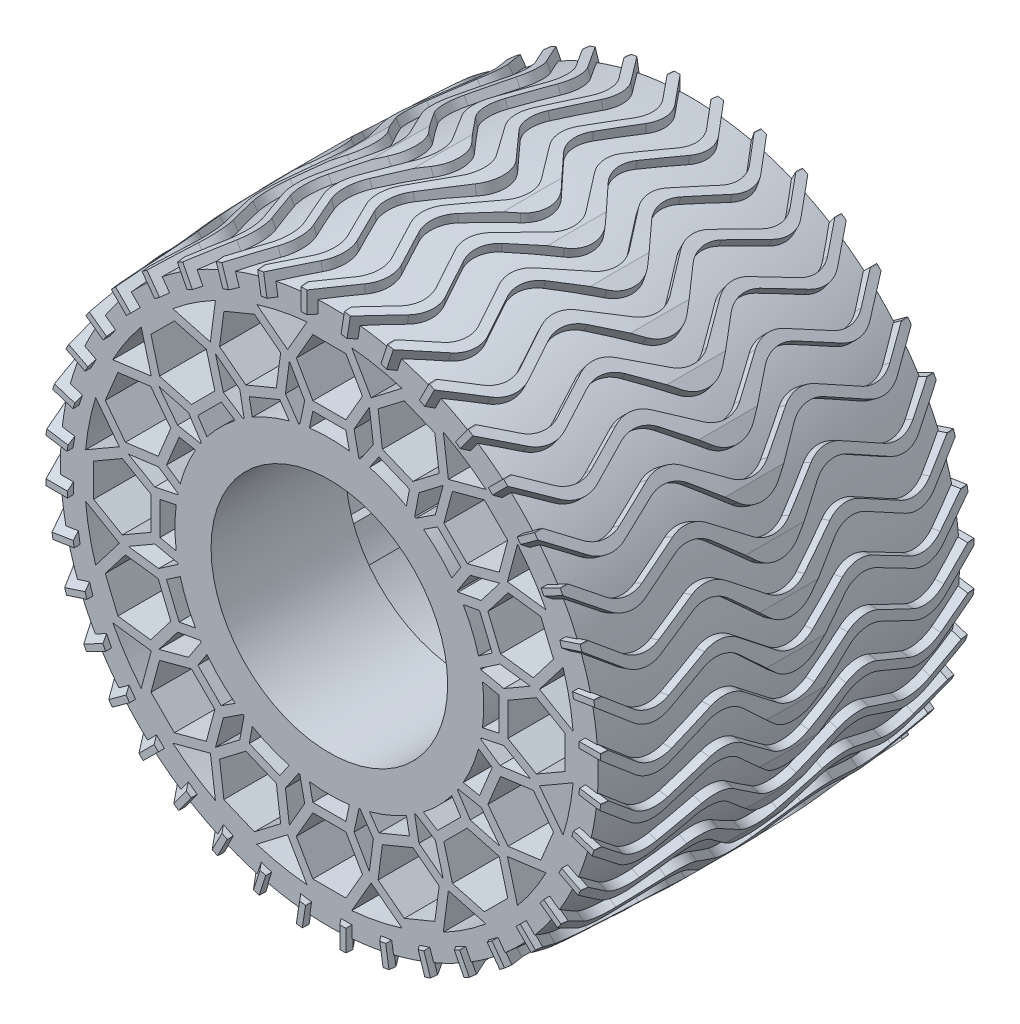
SolidWorks part; units mm, degrees
ref_plane "Alzado" through (0, 0, 0) normal (0, 0, 1) x (1, 0, 0)
ref_plane "Planta" through (0, 0, 0) normal (0, 1, 0) x (1, 0, 0)
ref_plane "Vista lateral" through (0, 0, 0) normal (1, 0, 0) x (0, 0, -1)
sketch "Croquis3" plane through (0, 0, 0) normal (1, 0, 0) x (0, 0, -1)
  line L0 (-55, 0) -> (55, 0) construction
  point P4 (0, 0)
  dimension "D1" = 110
sketch "Croquis2" plane through (0, 0, 0) normal (1, 0, 0) x (0, 0, -1)
  line L0 (0, 0) -> (0, 81.3) construction
  line L1 (-60, 81.3) -> (60, 81.3)
  line L2 (0, 81.3) -> (0, 89.3) construction
  line L3 (0, 89.3) -> (0, 92.3) construction
  line L4 (-60, 89.3) -> (60, 89.3) construction
  line L5 (-60, 89.3) -> (-60, 81.3)
  line L6 (60, 89.3) -> (60, 81.3)
  line L7 (-60, 39.3) -> (-15.3, 39.3)
  line L8 (60, 39.3) -> (60, 51.3)
  line L9 (60, 51.3) -> (-60, 51.3)
  line L10 (-60, 51.3) -> (-60, 39.3)
  line L11 (-50, 47.9) -> (50, 47.9)
  line L14 (50, 39.3) -> (60, 39.3)
  line L15 (-15.3, 39.3) -> (-15.3, 42.3)
  line L16 (-15.3, 42.3) -> (-50, 42.3)
  line L17 (-50, 42.3) -> (-50, 47.9)
  line L20 (50, 39.3) -> (50, 47.9)
  arc A0 (60, 89.3) -> (-60, 89.3) centre (0, -509.2) ccw
  point P6 (0, 81.3)
  point P11 (0, 89.3)
  point P15 (0, 39.3)
  point P18 (0, 51.3)
  point P20 (0, 47.9)
  dimension "D2" = 120
  dimension "D3" = 8
  dimension "D4" = 3
  dimension "D5" = 12
  dimension "D6" = 39.3
  dimension "D7" = 100
  dimension "D8" = 15.3
  dimension "D10" = 30
  dimension "D12" = 3
  dimension "D13" = 5.6
revolve "Revolución1" add sketch "Croquis2" angle 360 about L0
sketch "Croquis4" plane through (0, 0, 0) normal (0, 0, 1) x (1, 0, 0)
  line L0 (-72.3472, 37.7855) -> (-77.8756, 24.4389)
  line L1 (77.8756, 24.4389) -> (72.3472, 37.7855)
  line L2 (62.5953, 52.3803) -> (52.3803, 62.5953)
  line L3 (37.7855, 72.3472) -> (24.4389, 77.8756)
  line L4 (7.2231, 81.3) -> (-7.2231, 81.3)
  line L5 (-24.4389, 77.8756) -> (-37.7855, 72.3472)
  line L6 (-52.3803, 62.5953) -> (-62.5953, 52.3803)
  line L7 (-81.3, 7.2231) -> (-81.3, -7.2231)
  line L8 (-77.8756, -24.4389) -> (-72.3472, -37.7855)
  line L9 (-62.5953, -52.3803) -> (-52.3803, -62.5953)
  line L10 (-37.7855, -72.3472) -> (-24.4389, -77.8756)
  line L11 (-7.2231, -81.3) -> (7.2231, -81.3)
  line L12 (24.4389, -77.8756) -> (37.7855, -72.3472)
  line L13 (52.3803, -62.5953) -> (62.5953, -52.3803)
  line L14 (72.3472, -37.7855) -> (77.8756, -24.4389)
  line L15 (81.3, -7.2231) -> (81.3, 7.2231)
  line L16 (0, 0) -> (81.3, 0) construction
  line L17 (15.3929, 77.3853) -> (-14.444, -72.6147) construction
  line L18 (-14.9184, 75) -> (14.9184, -75) construction
  line L19 (0, 0) -> (0, 81.3) construction
  line L20 (-7.2231, 81.3) -> (-13.8786, 69.7724)
  line L31 (-13.2819, 66.7724) -> (-8.2005, 57.9713)
  line L32 (-8.2005, 57.9713) -> (-9.9128, 49.8349)
  line L33 (-7.1326, 48.4781) -> (-5.4911, 56.2784)
  line L34 (10.9821, 68.7892) -> (5.4911, 78.3)
  line L35 (5.4911, 78.3) -> (-5.4911, 78.3)
  line L36 (-5.4911, 78.3) -> (-10.9821, 68.7892)
  line L37 (-10.9821, 68.7892) -> (-5.4911, 59.2784)
  line L38 (-5.4911, 59.2784) -> (5.4911, 59.2784)
  line L39 (5.4911, 59.2784) -> (10.9821, 68.7892)
  line L40 (-5.4911, 56.2784) -> (5.4911, 56.2784)
  line L41 (5.4911, 56.2784) -> (7.1326, 48.4781)
  line L42 (36.4707, 59.3502) -> (35.0372, 70.2384)
  line L43 (35.0372, 70.2384) -> (24.891, 74.4411)
  line L44 (24.891, 74.4411) -> (16.1783, 67.7556)
  line L45 (16.1783, 67.7556) -> (17.6118, 56.8674)
  line L46 (17.6118, 56.8674) -> (27.7579, 52.6647)
  line L47 (8.2005, 57.9713) -> (9.9128, 49.8349)
  line L48 (27.7579, 52.6647) -> (36.4707, 59.3502)
  line L49 (13.2819, 66.7724) -> (8.2005, 57.9713)
  line L50 (7.2231, 81.3) -> (13.8786, 69.7724)
  line L51 (24.4389, 77.8756) -> (13.8786, 69.7724)
  line L52 (13.2819, 66.7724) -> (14.6083, 56.6967)
  line L53 (11.9621, 47.5174) -> (16.4637, 54.0958)
  line L54 (14.6083, 56.6967) -> (9.9128, 49.8349)
  line L55 (26.6099, 49.8931) -> (25.1414, 42.0584)
  line L56 (29.7609, 50.4203) -> (28.2292, 42.248)
  line L57 (16.4637, 54.0958) -> (26.6099, 49.8931)
  line L58 (37.8235, 56.6069) -> (29.7609, 50.4203)
  line L59 (37.7855, 72.3472) -> (39.5229, 59.1502)
  line L60 (56.4068, 40.8757) -> (59.2492, 51.4837)
  line L61 (59.2492, 51.4837) -> (51.4837, 59.2492)
  line L62 (51.4837, 59.2492) -> (40.8757, 56.4068)
  line L63 (40.8757, 56.4068) -> (38.0334, 45.7989)
  line L64 (38.0334, 45.7989) -> (45.7989, 38.0334)
  line L65 (45.7989, 38.0334) -> (56.4068, 40.8757)
  line L66 (52.3803, 62.5953) -> (39.5229, 59.1502)
  line L67 (37.8235, 56.6069) -> (35.1932, 46.7905)
  line L68 (29.2357, 39.3227) -> (35.912, 43.6776)
  line L69 (35.1932, 46.7905) -> (28.2292, 42.248)
  line L70 (43.6776, 35.912) -> (39.3227, 29.2357)
  line L71 (46.7905, 35.1932) -> (42.248, 28.2292)
  line L72 (35.912, 43.6776) -> (43.6776, 35.912)
  line L73 (56.6069, 37.8235) -> (46.7905, 35.1932)
  line L74 (62.5953, 52.3803) -> (59.1502, 39.5229)
  line L75 (67.7556, 16.1783) -> (74.4411, 24.891)
  line L76 (74.4411, 24.891) -> (70.2384, 35.0372)
  line L77 (70.2384, 35.0372) -> (59.3502, 36.4707)
  line L78 (59.3502, 36.4707) -> (52.6647, 27.7579)
  line L79 (52.6647, 27.7579) -> (56.8674, 17.6118)
  line L80 (56.8674, 17.6118) -> (67.7556, 16.1783)
  line L81 (72.3472, 37.7855) -> (59.1502, 39.5229)
  line L82 (56.6069, 37.8235) -> (50.4203, 29.7609)
  line L83 (42.0584, 25.1414) -> (49.8931, 26.6099)
  line L84 (50.4203, 29.7609) -> (42.248, 28.2292)
  line L85 (54.0958, 16.4637) -> (47.5174, 11.9621)
  line L86 (56.6967, 14.6083) -> (49.8349, 9.9128)
  line L87 (49.8931, 26.6099) -> (54.0958, 16.4637)
  line L88 (66.7724, 13.2819) -> (56.6967, 14.6083)
  line L89 (77.8756, 24.4389) -> (69.7724, 13.8786)
  line L90 (68.7892, -10.9821) -> (78.3, -5.4911)
  line L91 (78.3, -5.4911) -> (78.3, 5.4911)
  line L92 (78.3, 5.4911) -> (68.7892, 10.9821)
  line L93 (68.7892, 10.9821) -> (59.2784, 5.4911)
  line L94 (59.2784, 5.4911) -> (59.2784, -5.4911)
  line L95 (59.2784, -5.4911) -> (68.7892, -10.9821)
  line L96 (81.3, 7.2231) -> (69.7724, 13.8786)
  line L97 (66.7724, 13.2819) -> (57.9713, 8.2005)
  line L98 (48.4781, 7.1326) -> (56.2784, 5.4911)
  line L99 (57.9713, 8.2005) -> (49.8349, 9.9128)
  line L100 (56.2784, -5.4911) -> (48.4781, -7.1326)
  line L101 (57.9713, -8.2005) -> (49.8349, -9.9128)
  line L102 (56.2784, 5.4911) -> (56.2784, -5.4911)
  line L103 (66.7724, -13.2819) -> (57.9713, -8.2005)
  line L104 (81.3, -7.2231) -> (69.7724, -13.8786)
  line L105 (59.3502, -36.4707) -> (70.2384, -35.0372)
  line L106 (70.2384, -35.0372) -> (74.4411, -24.891)
  line L107 (74.4411, -24.891) -> (67.7556, -16.1783)
  line L108 (67.7556, -16.1783) -> (56.8674, -17.6118)
  line L109 (56.8674, -17.6118) -> (52.6647, -27.7579)
  line L110 (52.6647, -27.7579) -> (59.3502, -36.4707)
  line L111 (77.8756, -24.4389) -> (69.7724, -13.8786)
  line L112 (66.7724, -13.2819) -> (56.6967, -14.6083)
  line L113 (47.5174, -11.9621) -> (54.0958, -16.4637)
  line L114 (56.6967, -14.6083) -> (49.8349, -9.9128)
  line L115 (49.8931, -26.6099) -> (42.0584, -25.1414)
  line L116 (50.4203, -29.7609) -> (42.248, -28.2292)
  line L117 (54.0958, -16.4637) -> (49.8931, -26.6099)
  line L118 (56.6069, -37.8235) -> (50.4203, -29.7609)
  line L119 (72.3472, -37.7855) -> (59.1502, -39.5229)
  line L120 (40.8757, -56.4068) -> (51.4837, -59.2492)
  line L121 (51.4837, -59.2492) -> (59.2492, -51.4837)
  line L122 (59.2492, -51.4837) -> (56.4068, -40.8757)
  line L123 (56.4068, -40.8757) -> (45.7989, -38.0334)
  line L124 (45.7989, -38.0334) -> (38.0334, -45.7989)
  line L125 (38.0334, -45.7989) -> (40.8757, -56.4068)
  line L126 (62.5953, -52.3803) -> (59.1502, -39.5229)
  line L127 (56.6069, -37.8235) -> (46.7905, -35.1932)
  line L128 (39.3227, -29.2357) -> (43.6776, -35.912)
  line L129 (46.7905, -35.1932) -> (42.248, -28.2292)
  line L130 (35.912, -43.6776) -> (29.2357, -39.3227)
  line L131 (35.1932, -46.7905) -> (28.2292, -42.248)
  line L132 (43.6776, -35.912) -> (35.912, -43.6776)
  line L133 (37.8235, -56.6069) -> (35.1932, -46.7905)
  line L134 (52.3803, -62.5953) -> (39.5229, -59.1502)
  line L135 (16.1783, -67.7556) -> (24.891, -74.4411)
  line L136 (24.891, -74.4411) -> (35.0372, -70.2384)
  line L137 (35.0372, -70.2384) -> (36.4707, -59.3502)
  line L138 (36.4707, -59.3502) -> (27.7579, -52.6647)
  line L139 (27.7579, -52.6647) -> (17.6118, -56.8674)
  line L140 (17.6118, -56.8674) -> (16.1783, -67.7556)
  line L141 (37.7855, -72.3472) -> (39.5229, -59.1502)
  line L142 (37.8235, -56.6069) -> (29.7609, -50.4203)
  line L143 (25.1414, -42.0584) -> (26.6099, -49.8931)
  line L144 (29.7609, -50.4203) -> (28.2292, -42.248)
  line L145 (16.4637, -54.0958) -> (11.9621, -47.5174)
  line L146 (14.6083, -56.6967) -> (9.9128, -49.8349)
  line L147 (26.6099, -49.8931) -> (16.4637, -54.0958)
  line L148 (13.2819, -66.7724) -> (14.6083, -56.6967)
  line L149 (24.4389, -77.8756) -> (13.8786, -69.7724)
  line L150 (-10.9821, -68.7892) -> (-5.4911, -78.3)
  line L151 (-5.4911, -78.3) -> (5.4911, -78.3)
  line L152 (5.4911, -78.3) -> (10.9821, -68.7892)
  line L153 (10.9821, -68.7892) -> (5.4911, -59.2784)
  line L154 (5.4911, -59.2784) -> (-5.4911, -59.2784)
  line L155 (-5.4911, -59.2784) -> (-10.9821, -68.7892)
  line L156 (7.2231, -81.3) -> (13.8786, -69.7724)
  line L157 (13.2819, -66.7724) -> (8.2005, -57.9713)
  line L158 (7.1326, -48.4781) -> (5.4911, -56.2784)
  line L159 (8.2005, -57.9713) -> (9.9128, -49.8349)
  line L160 (-5.4911, -56.2784) -> (-7.1326, -48.4781)
  line L161 (-8.2005, -57.9713) -> (-9.9128, -49.8349)
  line L162 (5.4911, -56.2784) -> (-5.4911, -56.2784)
  line L163 (-13.2819, -66.7724) -> (-8.2005, -57.9713)
  line L164 (-7.2231, -81.3) -> (-13.8786, -69.7724)
  line L165 (-36.4707, -59.3502) -> (-35.0372, -70.2384)
  line L166 (-35.0372, -70.2384) -> (-24.891, -74.4411)
  line L167 (-24.891, -74.4411) -> (-16.1783, -67.7556)
  line L168 (-16.1783, -67.7556) -> (-17.6118, -56.8674)
  line L169 (-17.6118, -56.8674) -> (-27.7579, -52.6647)
  line L170 (-27.7579, -52.6647) -> (-36.4707, -59.3502)
  line L171 (-24.4389, -77.8756) -> (-13.8786, -69.7724)
  line L172 (-13.2819, -66.7724) -> (-14.6083, -56.6967)
  line L173 (-11.9621, -47.5174) -> (-16.4637, -54.0958)
  line L174 (-14.6083, -56.6967) -> (-9.9128, -49.8349)
  line L175 (-26.6099, -49.8931) -> (-25.1414, -42.0584)
  line L176 (-29.7609, -50.4203) -> (-28.2292, -42.248)
  line L177 (-16.4637, -54.0958) -> (-26.6099, -49.8931)
  line L178 (-37.8235, -56.6069) -> (-29.7609, -50.4203)
  line L179 (-37.7855, -72.3472) -> (-39.5229, -59.1502)
  line L180 (-56.4068, -40.8757) -> (-59.2492, -51.4837)
  line L181 (-59.2492, -51.4837) -> (-51.4837, -59.2492)
  line L182 (-51.4837, -59.2492) -> (-40.8757, -56.4068)
  line L183 (-40.8757, -56.4068) -> (-38.0334, -45.7989)
  line L184 (-38.0334, -45.7989) -> (-45.7989, -38.0334)
  line L185 (-45.7989, -38.0334) -> (-56.4068, -40.8757)
  line L186 (-52.3803, -62.5953) -> (-39.5229, -59.1502)
  line L187 (-37.8235, -56.6069) -> (-35.1932, -46.7905)
  line L188 (-29.2357, -39.3227) -> (-35.912, -43.6776)
  line L189 (-35.1932, -46.7905) -> (-28.2292, -42.248)
  line L190 (-43.6776, -35.912) -> (-39.3227, -29.2357)
  line L191 (-46.7905, -35.1932) -> (-42.248, -28.2292)
  line L192 (-35.912, -43.6776) -> (-43.6776, -35.912)
  line L193 (-56.6069, -37.8235) -> (-46.7905, -35.1932)
  line L194 (-62.5953, -52.3803) -> (-59.1502, -39.5229)
  line L195 (-67.7556, -16.1783) -> (-74.4411, -24.891)
  line L196 (-74.4411, -24.891) -> (-70.2384, -35.0372)
  line L197 (-70.2384, -35.0372) -> (-59.3502, -36.4707)
  line L198 (-59.3502, -36.4707) -> (-52.6647, -27.7579)
  line L199 (-52.6647, -27.7579) -> (-56.8674, -17.6118)
  line L200 (-56.8674, -17.6118) -> (-67.7556, -16.1783)
  line L201 (-72.3472, -37.7855) -> (-59.1502, -39.5229)
  line L202 (-56.6069, -37.8235) -> (-50.4203, -29.7609)
  line L203 (-42.0584, -25.1414) -> (-49.8931, -26.6099)
  line L204 (-50.4203, -29.7609) -> (-42.248, -28.2292)
  line L205 (-54.0958, -16.4637) -> (-47.5174, -11.9621)
  line L206 (-56.6967, -14.6083) -> (-49.8349, -9.9128)
  line L207 (-49.8931, -26.6099) -> (-54.0958, -16.4637)
  line L208 (-66.7724, -13.2819) -> (-56.6967, -14.6083)
  line L209 (-77.8756, -24.4389) -> (-69.7724, -13.8786)
  line L210 (-68.7892, 10.9821) -> (-78.3, 5.4911)
  line L211 (-78.3, 5.4911) -> (-78.3, -5.4911)
  line L212 (-78.3, -5.4911) -> (-68.7892, -10.9821)
  line L213 (-68.7892, -10.9821) -> (-59.2784, -5.4911)
  line L214 (-59.2784, -5.4911) -> (-59.2784, 5.4911)
  line L215 (-59.2784, 5.4911) -> (-68.7892, 10.9821)
  line L216 (-81.3, -7.2231) -> (-69.7724, -13.8786)
  line L217 (-66.7724, -13.2819) -> (-57.9713, -8.2005)
  line L218 (-48.4781, -7.1326) -> (-56.2784, -5.4911)
  line L219 (-57.9713, -8.2005) -> (-49.8349, -9.9128)
  line L220 (-56.2784, 5.4911) -> (-48.4781, 7.1326)
  line L221 (-57.9713, 8.2005) -> (-49.8349, 9.9128)
  line L222 (-56.2784, -5.4911) -> (-56.2784, 5.4911)
  line L223 (-66.7724, 13.2819) -> (-57.9713, 8.2005)
  line L224 (-81.3, 7.2231) -> (-69.7724, 13.8786)
  line L225 (-59.3502, 36.4707) -> (-70.2384, 35.0372)
  line L226 (-70.2384, 35.0372) -> (-74.4411, 24.891)
  line L227 (-74.4411, 24.891) -> (-67.7556, 16.1783)
  line L228 (-67.7556, 16.1783) -> (-56.8674, 17.6118)
  line L229 (-56.8674, 17.6118) -> (-52.6647, 27.7579)
  line L230 (-52.6647, 27.7579) -> (-59.3502, 36.4707)
  line L231 (-77.8756, 24.4389) -> (-69.7724, 13.8786)
  line L232 (-66.7724, 13.2819) -> (-56.6967, 14.6083)
  line L233 (-47.5174, 11.9621) -> (-54.0958, 16.4637)
  line L234 (-56.6967, 14.6083) -> (-49.8349, 9.9128)
  line L235 (-49.8931, 26.6099) -> (-42.0584, 25.1414)
  line L236 (-50.4203, 29.7609) -> (-42.248, 28.2292)
  line L237 (-54.0958, 16.4637) -> (-49.8931, 26.6099)
  line L238 (-56.6069, 37.8235) -> (-50.4203, 29.7609)
  line L239 (-72.3472, 37.7855) -> (-59.1502, 39.5229)
  line L240 (-40.8757, 56.4068) -> (-51.4837, 59.2492)
  line L241 (-51.4837, 59.2492) -> (-59.2492, 51.4837)
  line L242 (-59.2492, 51.4837) -> (-56.4068, 40.8757)
  line L243 (-56.4068, 40.8757) -> (-45.7989, 38.0334)
  line L244 (-45.7989, 38.0334) -> (-38.0334, 45.7989)
  line L245 (-38.0334, 45.7989) -> (-40.8757, 56.4068)
  line L246 (-62.5953, 52.3803) -> (-59.1502, 39.5229)
  line L247 (-56.6069, 37.8235) -> (-46.7905, 35.1932)
  line L248 (-39.3227, 29.2357) -> (-43.6776, 35.912)
  line L249 (-46.7905, 35.1932) -> (-42.248, 28.2292)
  line L250 (-35.912, 43.6776) -> (-29.2357, 39.3227)
  line L251 (-35.1932, 46.7905) -> (-28.2292, 42.248)
  line L252 (-43.6776, 35.912) -> (-35.912, 43.6776)
  line L253 (-37.8235, 56.6069) -> (-35.1932, 46.7905)
  line L254 (-52.3803, 62.5953) -> (-39.5229, 59.1502)
  line L255 (-16.1783, 67.7556) -> (-24.891, 74.4411)
  line L256 (-24.891, 74.4411) -> (-35.0372, 70.2384)
  line L257 (-35.0372, 70.2384) -> (-36.4707, 59.3502)
  line L258 (-36.4707, 59.3502) -> (-27.7579, 52.6647)
  line L259 (-27.7579, 52.6647) -> (-17.6118, 56.8674)
  line L260 (-17.6118, 56.8674) -> (-16.1783, 67.7556)
  line L261 (-37.7855, 72.3472) -> (-39.5229, 59.1502)
  line L262 (-37.8235, 56.6069) -> (-29.7609, 50.4203)
  line L263 (-25.1414, 42.0584) -> (-26.6099, 49.8931)
  line L264 (-29.7609, 50.4203) -> (-28.2292, 42.248)
  line L265 (-16.4637, 54.0958) -> (-11.9621, 47.5174)
  line L266 (-14.6083, 56.6967) -> (-9.9128, 49.8349)
  line L267 (-26.6099, 49.8931) -> (-16.4637, 54.0958)
  line L268 (-13.2819, 66.7724) -> (-14.6083, 56.6967)
  line L269 (-24.4389, 77.8756) -> (-13.8786, 69.7724)
  arc A0 (-24.1281, 77.6371) -> (-37.8366, 71.9589) centre (0, 0) ccw construction
  circle A1 centre (0, 0) radius 81.3 construction
  circle A5 centre (0, 68.7892) radius 9.5108 construction
  arc A9 (-39.3227, 29.2357) -> (-42.0584, 25.1414) centre (0, 0) ccw
  arc A41 (7.419, 80.9608) -> (-7.419, 80.9608) centre (0, 0) ccw construction
  arc A42 (37.8366, 71.9589) -> (24.1281, 77.6371) centre (0, 0) ccw construction
  arc A43 (62.4939, 52.0019) -> (52.0019, 62.4939) centre (0, 0) ccw construction
  arc A44 (77.6371, 24.1281) -> (71.9589, 37.8366) centre (0, 0) ccw construction
  arc A45 (80.9608, -7.419) -> (80.9608, 7.419) centre (0, 0) ccw construction
  arc A46 (71.9589, -37.8366) -> (77.6371, -24.1281) centre (0, 0) ccw construction
  arc A47 (52.0019, -62.4939) -> (62.4939, -52.0019) centre (0, 0) ccw construction
  arc A48 (24.1281, -77.6371) -> (37.8366, -71.9589) centre (0, 0) ccw construction
  arc A49 (-7.419, -80.9608) -> (7.419, -80.9608) centre (0, 0) ccw construction
  arc A50 (-37.8366, -71.9589) -> (-24.1281, -77.6371) centre (0, 0) ccw construction
  arc A51 (-62.4939, -52.0019) -> (-52.0019, -62.4939) centre (0, 0) ccw construction
  arc A52 (-77.6371, -24.1281) -> (-71.9589, -37.8366) centre (0, 0) ccw construction
  arc A53 (-80.9608, 7.419) -> (-80.9608, -7.419) centre (0, 0) ccw construction
  arc A54 (-71.9589, 37.8366) -> (-77.6371, 24.1281) centre (0, 0) ccw construction
  arc A55 (-52.0019, 62.4939) -> (-62.4939, 52.0019) centre (0, 0) ccw construction
  arc A64 (-25.1414, 42.0584) -> (-29.2357, 39.3227) centre (0, 0) ccw
  arc A65 (-7.1326, 48.4781) -> (-11.9621, 47.5174) centre (0, 0) ccw
  arc A66 (11.9621, 47.5174) -> (7.1326, 48.4781) centre (0, 0) ccw
  arc A67 (29.2357, 39.3227) -> (25.1414, 42.0584) centre (0, 0) ccw
  arc A68 (42.0584, 25.1414) -> (39.3227, 29.2357) centre (0, 0) ccw
  arc A69 (49, 0) -> (47.5174, 11.9621) centre (0, 0) ccw
  arc A70 (47.5174, -11.9621) -> (48.4781, -7.1326) centre (0, 0) ccw
  arc A71 (39.3227, -29.2357) -> (42.0584, -25.1414) centre (0, 0) ccw
  arc A72 (25.1414, -42.0584) -> (29.2357, -39.3227) centre (0, 0) ccw
  arc A73 (7.1326, -48.4781) -> (11.9621, -47.5174) centre (0, 0) ccw
  arc A74 (-11.9621, -47.5174) -> (-7.1326, -48.4781) centre (0, 0) ccw
  arc A75 (-29.2357, -39.3227) -> (-25.1414, -42.0584) centre (0, 0) ccw
  arc A76 (-42.0584, -25.1414) -> (-39.3227, -29.2357) centre (0, 0) ccw
  arc A77 (-48.4781, -7.1326) -> (-47.5174, -11.9621) centre (0, 0) ccw
  arc A78 (-47.5174, 11.9621) -> (-48.4781, 7.1326) centre (0, 0) ccw
  point P1 (81.3, 0)
  point P38 (0, 52.383)
  point P385 (0, 0)
  dimension "D7" = 3
  dimension "D10" = 98
  dimension "D1" = 3
  dimension "D2" = 3
  dimension "D3" = 3
  dimension "D4" = 3
  dimension "D5" = 3
  dimension "D8" = 3
  dimension "D9" = 16
extrude "Saliente-Extruir1" add sketch "Croquis4" along normal mid plane 120 contours L269 L5 L261 L254 L6 L246 L239 L0 L231 L224 L7 L216 L209 L8 L201 L194 L9 L186 L179 L10 L171 L164 L11 L156 L149 L12 L141 L134 L13 L126 L119 L14 L111 L104 L15 L96 L89 L1 L81 L74 L2 L66 L59 L3 L51 L50 L4 L20 A78 L233 region at (-65.4486, 36.3743, 0)
sketch "Croquis5" plane through (0, 0, 0) normal (0, 0, 1) x (1, 0, 0)
  line L0 (0, 0) -> (0, 38.9) construction
  line L1 (5.3021, 41.9664) -> (6.1796, 48.9112)
  line L2 (-5.3021, 41.9664) -> (-6.1796, 48.9112)
  line L3 (38.995, -16.3914) -> (45.4481, -19.1039)
  line L4 (33.6929, -25.575) -> (39.2685, -29.8072)
  line L5 (-33.6929, -25.575) -> (-39.2685, -29.8072)
  line L6 (-38.995, -16.3914) -> (-45.4481, -19.1039)
  arc A1 (6.1796, 48.9112) -> (-6.1796, 48.9112) centre (0, 0) ccw
  arc A3 (-45.4481, -19.1039) -> (-39.2685, -29.8072) centre (0, 0) ccw
  arc A5 (39.2685, -29.8072) -> (45.4481, -19.1039) centre (0, 0) ccw
  arc A6 (5.3021, 41.9664) -> (-5.3021, 41.9664) centre (0, 0) ccw
  circle A8 centre (0, 0) radius 42.3 construction
  arc A9 (-38.995, -16.3914) -> (-33.6929, -25.575) centre (0, 0) ccw
  arc A10 (33.6929, -25.575) -> (38.995, -16.3914) centre (0, 0) ccw
  point P14 (0, 0)
  dimension "D1" = 38.9
  dimension "D3" = 3
extrude "Saliente-Extruir2" add sketch "Croquis5" along normal mid plane 120
ref_plane "Plano1" through (0, 90, 0) normal (0, 1, 0) x (1, 0, 0)
sketch "Croquis6" plane through (0, 90, 0) normal (0, 1, 0) x (1, 0, 0)
  line L0 (0, -62) -> (0, 62) construction
  line L1 (-4.1939, 17.3976) -> (4.3798, 6.0921)
  line L2 (4.3321, -6.0556) -> (-4.2317, -17.1652)
  line L3 (0.2503, 17.5515) -> (10.2102, 6.7937)
  line L4 (10.2102, -6.7937) -> (0.2503, -17.5515)
  line L5 (0, 62) -> (7.5, 62) construction
  line L6 (7.5, 62) -> (7.5, -62) construction
  line L7 (7.5, -62) -> (0, -62) construction
  line L8 (0, -62) -> (-7.5, -62) construction
  line L9 (-7.5, -62) -> (-7.5, 62) construction
  line L10 (-7.5, 62) -> (0, 62) construction
  line L12 (-1.3436, 28.842) -> (4.5493, 40.5468)
  line L13 (3.2981, 51.4474) -> (-5.5, 62)
  line L14 (-5.5, 62) -> (-7.5, 62)
  line L15 (-7.5, 62) -> (-7.5, 59.714)
  line L16 (-7.5, 59.714) -> (-0.2666, 51.0382)
  line L17 (0.9846, 40.1377) -> (-5.158, 27.9371)
  line L19 (0, 0) -> (-11.8513, 0) construction
  line L22 (0.9846, -40.1377) -> (-5.2435, -27.7672)
  line L23 (-1.3436, -28.842) -> (4.5493, -40.5468)
  line L24 (-7.5, -59.714) -> (-0.2666, -51.0382)
  line L25 (3.2981, -51.4474) -> (-5.5, -62)
  line L26 (-7.5, -62) -> (-7.5, -59.714)
  line L27 (-5.5, -62) -> (-7.5, -62)
  arc A0 (0.9846, -40.1377) -> (-0.2666, -51.0382) centre (-7.9473, -44.6345) cw
  arc A1 (4.5493, -40.5468) -> (3.2981, -51.4474) centre (-4.3825, -45.0437) cw
  arc A2 (0.2503, -17.5515) -> (-1.3436, -28.842) centre (7.5883, -24.3452) ccw
  arc A3 (-4.2317, -17.1652) -> (-5.2435, -27.7672) centre (3.6884, -23.2703) ccw
  arc A6 (0.2503, 17.5515) -> (-1.3436, 28.842) centre (7.5883, 24.3452) cw
  arc A7 (-5.158, 27.9371) -> (-4.1939, 17.3976) centre (3.7739, 23.4402) ccw
  arc A8 (-0.2666, 51.0382) -> (0.9846, 40.1377) centre (-7.9473, 44.6345) cw
  arc A9 (4.5493, 40.5468) -> (3.2981, 51.4474) centre (-4.3825, 45.0437) ccw
  arc A10 (10.2102, 6.7937) -> (10.2102, -6.7937) centre (2.8722, 0) cw
  arc A11 (4.3798, 6.0921) -> (4.3321, -6.0556) centre (-3.588, 0.0495) cw
  point P4 (0, 0)
  point P28 (3.9352, -45.9984)
  point P31 (7.5, -46.4076)
  point P34 (-4.1435, -23.2807)
  point P37 (-7.5, -23.2852)
  point P39 (16.5, 0)
  point P41 (7.5, 0)
  point P44 (-4.1435, 23.2807)
  point P47 (-7.5, 23.2852)
  point P50 (3.9352, 45.9984)
  point P53 (7.5, 46.4076)
  point P55 (9, 0)
  dimension "D8" = 10
  dimension "D10" = 10
  dimension "D1" = 124
  dimension "D2" = 15
  dimension "D3" = 7.5
  dimension "D4" = 2
  dimension "D5" = 3
  dimension "D6" = 3
  dimension "D7" = 7.5
  dimension "D9" = 1.5
extrude "Saliente-Extruir3" add sketch "Croquis6" along normal blind 12.5 and the other way blind 5
sketch "Croquis7" plane through (0, 0, 0) normal (1, 0, 0) x (0, 0, -1)
  line L0 (0, 0) -> (0, 92) construction
  line L1 (0, 92) -> (0, 95) construction
  line L2 (-60, 89.3) -> (-60, 92.3) construction
  line L3 (60, 89.3) -> (60, 92.3) construction
  line L4 (-62, 92.1166) -> (-62, 112.8498)
  line L5 (-62, 112.8498) -> (62, 112.8498)
  line L6 (62, 112.8498) -> (62, 92.1166)
  line L7 (-62, 85) -> (-62, 102.5) construction
  line L8 (62, 85) -> (62, 102.5) construction
  arc A0 (62, 92.1166) -> (-62, 92.1166) centre (0, -573.0167) ccw
  dimension "D1" = 92
  dimension "D2" = 3
  dimension "D3" = 3
extrude "Cortar-Extruir1" cut sketch "Croquis7" against normal mid plane 30
pattern_circular "MatrizC1" count 40 over 360 about axis through (0, 0, 55) along (0, 0, -1) of "Saliente-Extruir3", "Cortar-Extruir1"
